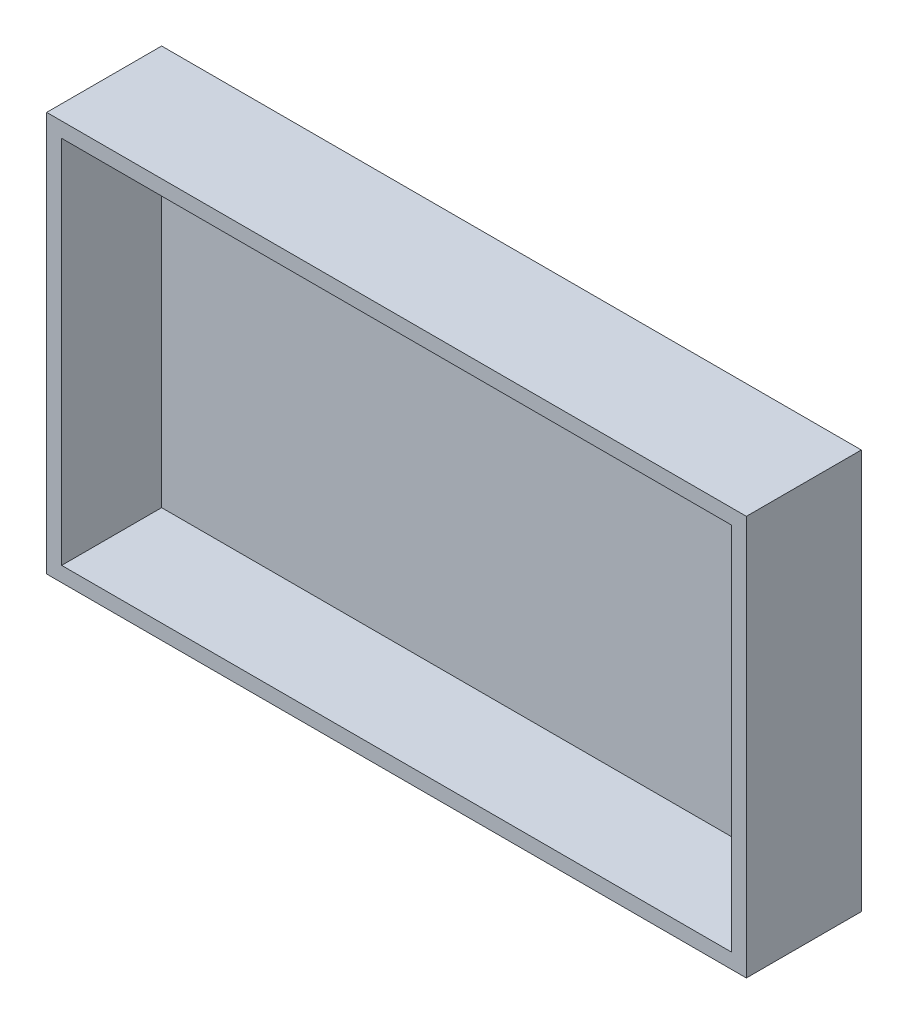
SolidWorks part; units mm, degrees
ref_plane "前视基准面" through (0, 0, 0) normal (0, 0, 1) x (1, 0, 0)
ref_plane "上视基准面" through (0, 0, 0) normal (0, 1, 0) x (1, 0, 0)
ref_plane "右视基准面" through (0, 0, 0) normal (1, 0, 0) x (0, 0, -1)
sketch "草图1" plane through (0, 0, 0) normal (0, 0, 1) x (1, 0, 0)
  line L1 (-35, 20) -> (35, 20)
  line L2 (-35, 20) -> (-35, -20)
  line L3 (-35, -20) -> (35, -20)
  line L4 (35, 20) -> (35, -20)
  line L5 (-35, 20) -> (35, -20) construction
  line L6 (-35, -20) -> (35, 20) construction
  point P0 (0, 0)
  dimension "D1" = 40
  dimension "D2" = 70
extrude "凸台-拉伸1" add sketch "草图1" along normal blind 11.5
shell "抽壳1" thickness 1.5 removed face at (0, 0, 11.5)
